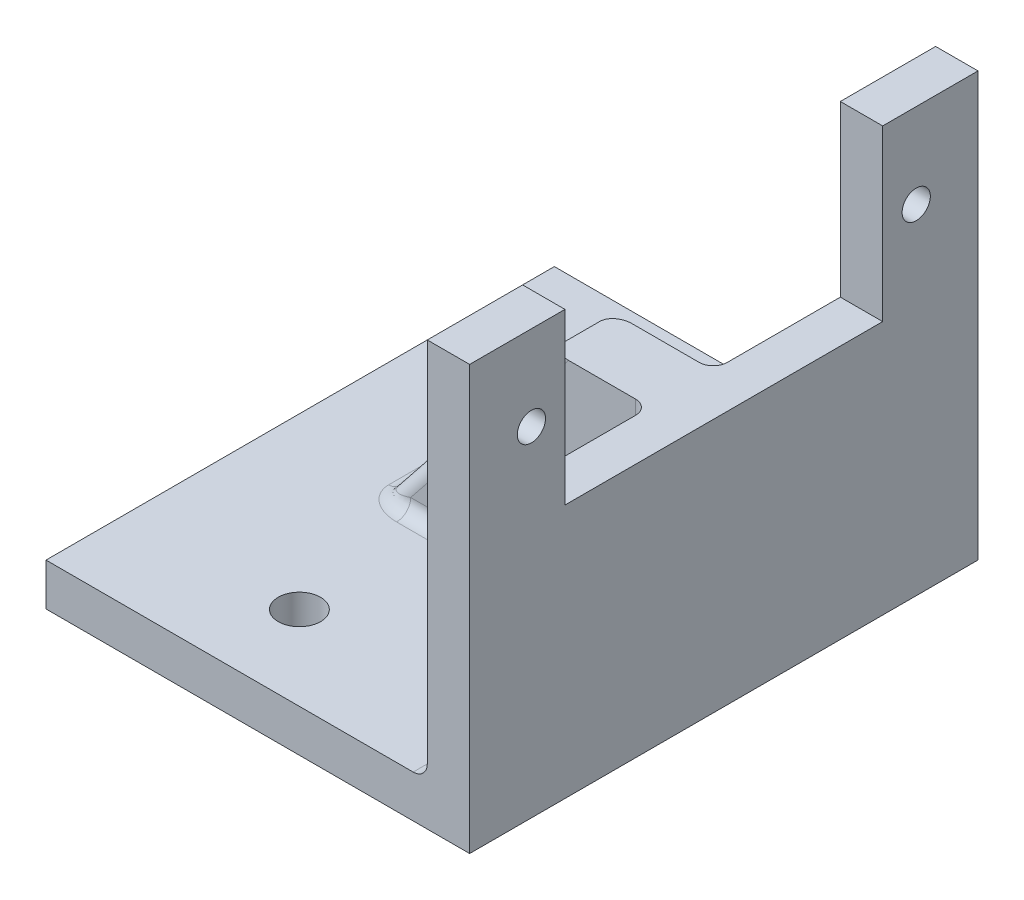
SolidWorks part; units mm, degrees
ref_plane "Front Plane" through (0, 0, 0) normal (0, 0, 1) x (1, 0, 0)
ref_plane "Top Plane" through (0, 0, 0) normal (0, 1, 0) x (1, 0, 0)
ref_plane "Right Plane" through (0, 0, 0) normal (1, 0, 0) x (0, 0, -1)
sketch "Sketch1" plane through (0, 0, 0) normal (0, 0, 1) x (1, 0, 0)
  line L0 (0, 0) -> (0, 30)
  line L1 (0, 0) -> (-30, 0)
  dimension "D1" = 30
  dimension "D2" = 30
extrude "Extrude-Thin1" add sketch "Sketch1" along normal blind 36 thin thin type one direction wall 3
sketch "Sketch2" plane through (0, 0, 0) normal (1, 0, 0) x (0, 0, -1)
  line L0 (-36, 30) -> (0, 30) construction
  line L1 (-29.25, 30) -> (-6.75, 30)
  line L2 (-29.25, 30) -> (-29.25, 18)
  line L3 (-29.25, 18) -> (-6.75, 18)
  line L4 (-6.75, 30) -> (-6.75, 18)
  line L5 (-18, 0) -> (-18, 34.8164) construction
  line L6 (-36, 0) -> (0, 0) construction
  circle A0 centre (-31.625, 24) radius 1
  circle A1 centre (-4.375, 24) radius 1
  point P14 (-29.25, 24)
  dimension "D3" = 2
  dimension "D1" = 22.5
  dimension "D2" = 12
  dimension "D4" = 27.25
extrude "Cut-Extrude1" cut sketch "Sketch2" against normal through all
sketch "Sketch3" plane through (-3, 0, 0) normal (-1, 0, 0) x (0, 0, 1)
  line L0 (18, 18) -> (18, 3) construction
  line L1 (29.25, 18) -> (6.75, 18) construction
  line L2 (36, 3) -> (0, 3) construction
  line L4 (15.75, 18) -> (20.25, 18)
  line L5 (15.75, 18) -> (15.75, 3)
  line L6 (15.75, 3) -> (20.25, 3)
  line L7 (20.25, 18) -> (20.25, 3)
  dimension "D1" = 4.5
extrude "Boss-Extrude1" add sketch "Sketch3" along normal blind 19
sketch "Sketch5" plane through (0, 0, 20.25) normal (0, 0, 1) x (1, 0, 0)
  line L0 (-22, 18) -> (-22, 3)
  line L1 (-22, 3) -> (-10.0264, 18)
  line L2 (-22, 18) -> (-3, 18) construction
  line L3 (-10.0264, 18) -> (-22, 18)
extrude "Cut-Extrude2" cut sketch "Sketch5" against normal through all
fillet "Fillet2" radius 1 5 edges at (-12.5, 3, 15.75) (-12.5, 3, 20.25) (-22, 3, 18) (-16.0132, 10.5, 15.75) (-16.0132, 10.5, 20.25)
fillet "Fillet3" radius 1 6 edges at (-3, 3, 7.375) (-3, 3.2929, 15.4571) (-3, 3, 28.625) (-3, 3.2929, 20.5429) (-3, 11, 15.75) (-3, 11, 20.25)
sketch "Sketch6" plane through (0, 3, 0) normal (0, 1, 0) x (1, 0, 0)
  line L1 (-30, -36) -> (-30, 0) construction
  circle A0 centre (-18, -5.056) radius 1.5
  circle A1 centre (-18, -30.056) radius 1.5
  dimension "D1" = 3
  dimension "D2" = 3
  dimension "D3" = 25
  dimension "D4" = 12
extrude "Cut-Extrude3" cut sketch "Sketch6" against normal through all
